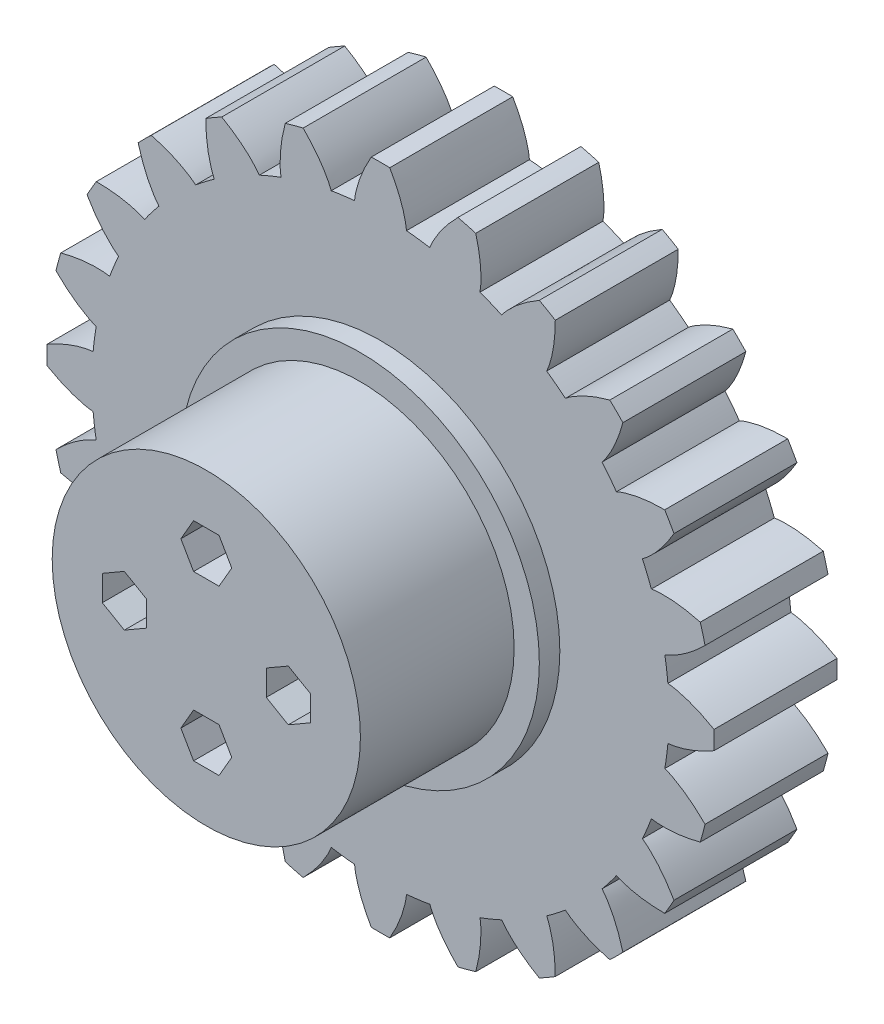
SolidWorks part; units mm, degrees
material "ABS"
ref_plane "Front Plane" through (0, 0, 0) normal (0, 0, 1) x (1, 0, 0)
ref_plane "Top Plane" through (0, 0, 0) normal (0, 1, 0) x (1, 0, 0)
ref_plane "Right Plane" through (0, 0, 0) normal (1, 0, 0) x (0, 0, -1)
sketch "Definition Drawing" plane through (0, 0, 0) normal (0, 0, 1) x (1, 0, 0)
  line L0 (16.2789, 0) -> (14.2789, 0) construction
  line L1 (0, 0) -> (-6.9516, 11.976) construction
  line L2 (0, 0) -> (0, 16.2789) construction
  line L3 (0, 0) -> (1.2743, 13.7886) construction
  line L4 (-6.9516, 11.976) -> (0.4506, 16.2726) construction
  line L5 (0, 0) -> (0.9494, 15.2493) construction
  line L6 (0, 0) -> (0.9993, 15.2462) construction
  line L7 (0, 0) -> (-5.0256, 12.9032) construction
  line L8 (-5.0256, 12.9032) -> (0.9558, 15.2329) construction
  line L9 (0, 0) -> (-2.9798, 13.5229) construction
  line L10 (-2.9798, 13.5229) -> (1.1993, 14.4438) construction
  line L11 (0, 0) -> (-0.8631, 13.8204) construction
  line L12 (-0.8631, 13.8204) -> (1.2725, 13.9538) construction
  circle A0 centre (0, 0) radius 13.8474 construction
  circle A1 centre (0, 0) radius 14.2789 construction
  circle A2 centre (0, 0) radius 15.2789 construction
  circle A3 centre (0, 0) radius 16.2789 construction
  circle A4 centre (0, 0) radius 14.0789 construction
  arc A5 (0.9494, 15.2493) -> (0.9993, 15.2462) centre (0, 0) cw construction
  spline S0 degree 3 poles (1.2743, 13.7886) (1.2817, 14.0092) (1.1458, 14.8862) (0.7794, 15.701) (0.4506, 16.2726) knots 0 0 0 0 0.250019 1 1 1 1 construction
  point P13 (15.2789, 0)
  dimension "D4" = 30.5577
  dimension "D5" = 27.6947
  dimension "D2" = 0.2
  dimension "D3" = 3.75
  dimension "D6" = 0.05
  dimension "D7" = 35.413
  dimension "D11" = 6.4191
  dimension "D12" = 4.2794
  dimension "D13" = 2.1397
  dimension "D8" = 26.56
  dimension "D9" = 17.707
  dimension "D10" = 8.853
sketch "Sketch5" plane through (0, 0, 0) normal (0, 0, 1) x (1, 0, 0)
  circle A1 centre (0, 0) radius 14.0789
  circle A2 centre (0, 0) radius 1.5
  circle A3 centre (0, 0) radius 14.0789 construction
  dimension "D1" = 3
extrude "Extrude Body" add sketch "Sketch5" along normal mid plane 6
sketch "Sketch6" plane through (0, 0, 0) normal (0, 0, 1) x (1, 0, 0)
  line L0 (0, 16.2789) -> (0, 0) construction
  line L4 (1.2743, 13.7886) -> (0.138, 1.4936)
  line L5 (0, 0) -> (1.2743, 13.7886) construction
  line L6 (-1.2743, 13.7886) -> (-0.138, 1.4936)
  arc A0 (0.4506, 16.2726) -> (-0.4506, 16.2726) centre (0, 0) ccw
  arc A3 (0.138, 1.4936) -> (-0.138, 1.4936) centre (0, 0) ccw
  circle A4 centre (0, 0) radius 1.5 construction
  spline S0 degree 3 poles (1.2743, 13.7886) (1.2817, 14.0092) (1.1458, 14.8862) (0.7794, 15.701) (0.4506, 16.2726) knots 0 0 0 0 0.250019 1 1 1 1
  spline S1 degree 3 poles (-1.2743, 13.7886) (-1.2817, 14.0092) (-1.1458, 14.8862) (-0.7794, 15.701) (-0.4506, 16.2726) knots 0 0 0 0 0.250019 1 1 1 1
extrude "Extrude Tooth" add sketch "Sketch6" along normal mid plane 6
pattern_circular "CirPattern1" count 24 over 360 about axis through (0, 0, 3) along (0, 0, -1) of "Extrude Tooth" reverse direction yes
sketch "Sketch8" plane through (0, 0, 0) normal (0, 0, 1) x (1, 0, 0)
  line L6 (0, 16.2789) -> (0, 0) construction
  line L7 (0, 0) -> (14.0979, -8.1394) construction
  line L8 (1.5, 9.7639) -> (1.5, 4.899)
  line L9 (4.9926, -1.1505) -> (9.2058, -3.5829)
  circle A2 centre (0, 0) radius 16.2789 construction
  arc A20 (10.6688, -2.9864) -> (2.748, 10.7326) centre (0, 0) ccw
  circle A21 centre (0, 0) radius 14.0789 construction
  arc A23 (9.2058, -3.5829) -> (10.6688, -2.9864) centre (9.7058, -2.7169) ccw
  arc A24 (4.9926, -1.1505) -> (4.494, -0.2327) centre (5.4926, -0.2844) cw
  arc A25 (1.5, 4.899) -> (2.0455, 4.0083) centre (2.5, 4.899) ccw
  arc A26 (1.5, 9.7639) -> (2.748, 10.7326) centre (2.5, 9.7639) cw
  arc A27 (4.494, -0.2327) -> (2.0455, 4.0083) centre (0, 0) ccw
  circle A28 centre (0, 0) radius 1.5 construction
  dimension "D1" = 3
  dimension "D6" = 1
  dimension "D4" = 3
  dimension "D5" = 3
  dimension "D2" = 3
  dimension "D3" = 120
extrude "Cut Spoke" cut sketch "Sketch8" against normal through all and the other way through all
pattern_circular "Pattern Spokes" count 3 over 360 about axis through (0, 0, 3) along (0, 0, -1) of "Cut Spoke"
scale "Scale1" scale about centroid uniform scaling yes scale factor 2
sketch "Sketch9" plane through (0, 0, 6) normal (0, 0, 1) x (1, 0, 0)
  circle A0 centre (0, 0) radius 24.5043
extrude "Boss-Extrude1" add sketch "Sketch9" against normal up to surface (12 mm away) up to face at (-10.0806, 5.82, 6)
sketch "Sketch10" plane through (0, 0, 6) normal (0, 0, 1) x (1, 0, 0)
  circle A0 centre (0, 0) radius 17.5
  dimension "D1" = 35
extrude "Boss-Extrude2" add sketch "Sketch10" along normal blind 2
sketch "Sketch11" plane through (0, 0, 8) normal (0, 0, 1) x (1, 0, 0)
  circle A0 centre (0, 0) radius 15.04
  dimension "D1" = 30.08
extrude "Boss-Extrude3" add sketch "Sketch11" along normal blind 15
sketch "Sketch12" plane through (0, 0, -6) normal (0, 0, -1) x (-1, 0, 0)
  line L0 (-8, 0) -> (8, 0) construction
  line L1 (0, 8) -> (0, -8) construction
  circle A0 centre (0, 8) radius 1.1
  circle A1 centre (8, 0) radius 1.1
  circle A2 centre (0, -8) radius 1.1
  circle A3 centre (-8, 0) radius 1.1
  point P4 (0, 0)
  point P5 (0, 0)
  dimension "D2" = 2.2
  dimension "D1" = 16
extrude "Cut-Extrude1" cut sketch "Sketch12" against normal blind 20
sketch "Sketch13" plane through (0, 0, -6) normal (0, 0, -1) x (-1, 0, 0)
  line L0 (1.2413, -10.15) -> (-1.2413, -10.15)
  line L1 (-1.2413, -10.15) -> (-2.4826, -8)
  line L2 (-2.4826, -8) -> (-1.2413, -5.85)
  line L3 (-1.2413, -5.85) -> (1.2413, -5.85)
  line L4 (1.2413, -5.85) -> (2.4826, -8)
  line L5 (2.4826, -8) -> (1.2413, -10.15)
  line L6 (1.2413, -10.15) -> (-1.2413, -5.85) construction
  line L7 (1.2413, -5.85) -> (-1.2413, -10.15) construction
  line L8 (2.4826, -8) -> (-2.4826, -8) construction
  circle A0 centre (0, -8) radius 1.1 construction
  point P2 (0, -8)
  dimension "D1" = 60
  dimension "D2" = 60
  dimension "D3" = 4.3
extrude "Cut-Extrude2" cut sketch "Sketch13" against normal up to surface (29 mm away) contours L0 L1 L2 L3 L4 L5 up to face at (15.04, 0, 23)
pattern_circular "CirPattern2" count 4 over 360 about axis through (0, 0, 6) along (0, 0, -1) of "Cut-Extrude2"
sketch "Sketch14" plane through (0, 0, -6) normal (0, 0, -1) x (-1, 0, 0)
  circle A0 centre (8, 0) radius 3.4316
  circle A1 centre (0, -8) radius 3.329
  circle A2 centre (-8, 0) radius 3.4653
  circle A3 centre (0, 8) radius 3.3566
extrude "Boss-Extrude4" add sketch "Sketch14" against normal blind 4
sketch "Sketch15" plane through (0, 0, -6) normal (0, 0, -1) x (-1, 0, 0)
  circle A0 centre (8, 0) radius 1.1
  circle A1 centre (0, -8) radius 1.1
  circle A2 centre (-8, 0) radius 1.1
  circle A3 centre (0, 8) radius 1.1
extrude "Cut-Extrude3" cut sketch "Sketch15" against normal up to next
equation "\"nTeeth\"= 24"
equation "\"xThickness\"= 6"
equation "\"dShaft\"= 3"
equation "\"aPressure\"=25"
equation "\"pitch\"= 4"
equation "\"rHeight\"= 2"
equation "\"rClearance\"= 0.2"
equation "\"xClearance\"=0.05"
equation "\"rFillet\"= 1"
equation "\"nSpokes\"= int ( ( \"nTeeth\" - 1 ) / 10 ) + 1'rounds up"
equation "\"dPitch\"= \"nTeeth\" * \"pitch\" / pi"
equation "\"xWall\"= IIF ( \"nTeeth\" > 30 , \"nTeeth\" / 10 , 3 )"
equation "\"dBase\"= \"dPitch\" * cos ( \"aPressure\" )"
equation "\"rOuter\"= \"dPitch\" / 2 + \"rHeight\" / 2"
equation "\"xInvolute\"= sqr ( \"rOuter\" ^ 2 - ( \"dBase\" / 2 ) ^ 2 )"
equation "\"aInvolute\"= 360 * \"xInvolute\" / ( \"dBase\" / 2 ) / 2 / pi"
equation "\"D1@Definition Drawing\" = \"rHeight\""
equation "\"D2@Definition Drawing\" = \"rClearance\""
equation "\"D4@Definition Drawing\" = \"dPitch\""
equation "\"D6@Definition Drawing\" = \"xClearance\""
equation "\"D5@Definition Drawing\" = \"dBase\""
equation "\"D7@Definition Drawing\" = \"aInvolute\""
equation "\"D11@Definition Drawing\" = \"xInvolute\" * 0.75"
equation "\"D12@Definition Drawing\" = \"xInvolute\" * 0.5"
equation "\"D13@Definition Drawing\" = \"xInvolute\" * 0.25"
equation "\"D8@Definition Drawing\" = \"aInvolute\" * 0.75"
equation "\"D9@Definition Drawing\" = \"aInvolute\" * 0.5"
equation "\"D10@Definition Drawing\" = \"aInvolute\" * 0.25"
equation "\"D1@Extrude Body\"=\"xThickness\""
equation "\"D1@Sketch5\"=\"dShaft\""
equation "\"D3@Definition Drawing\" = 360 / \"nTeeth\" / 2 / 2"
equation "\"D5@Sketch8\"=\"xWall\""
equation "\"D1@Sketch8\"=\"xWall\""
equation "\"D4@Sketch8\"=\"xWall\""
equation "\"D6@Sketch8\"=\"rFillet\""
equation "\"D1@Pattern Spokes\" = \"nSpokes\""
equation "\"rHub\"= IIF ( \"xWall\" * \"nSpokes\" / 6 > \"xWall\" , \"xWall\" * \"nSpokes\" / 6 , \"xWall\" )"
equation "\"D2@Sketch8\"=\"rHub\""
equation "\"D3@Sketch8\"=360/\"nSpokes\""
equation "\"D1@Extrude Tooth\" = \"xThickness\""
equation "\"D1@CirPattern1\"=\"nTeeth\""
